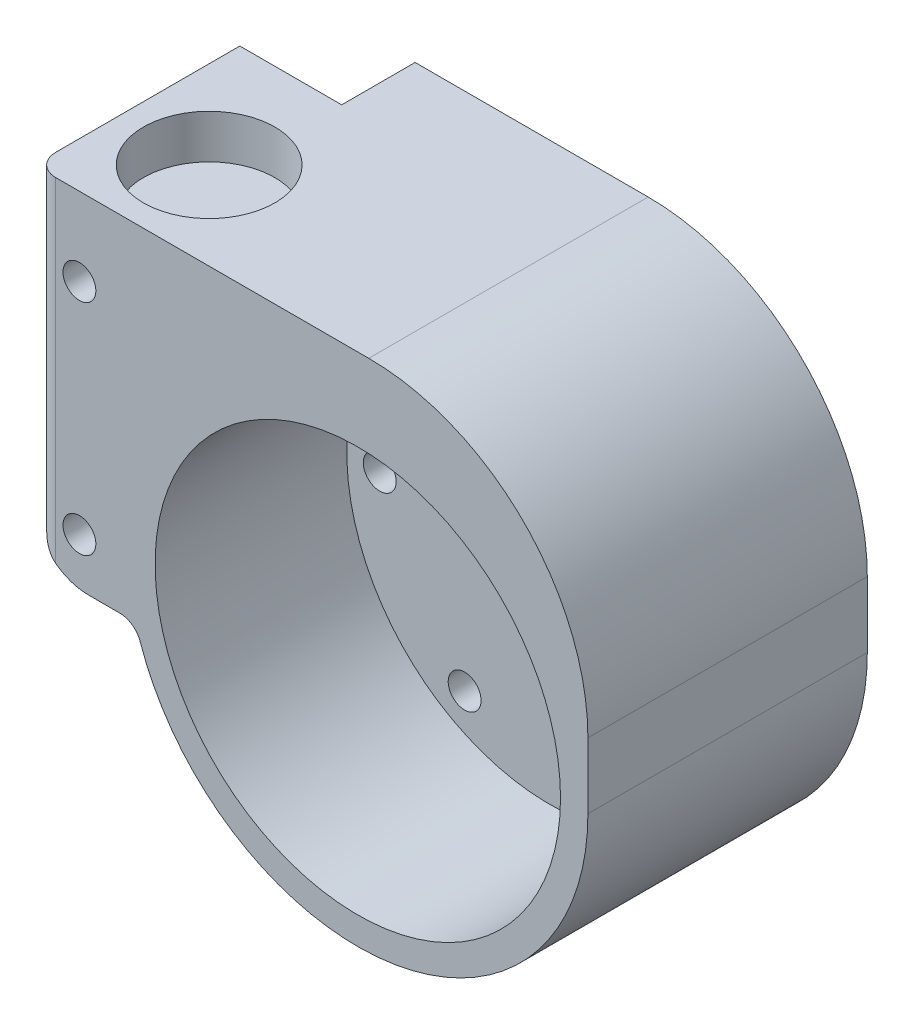
SolidWorks part; units mm, degrees
ref_plane "前视基准面" through (0, 0, 0) normal (0, 0, 1) x (1, 0, 0)
ref_plane "上视基准面" through (0, 0, 0) normal (0, 1, 0) x (1, 0, 0)
ref_plane "右视基准面" through (0, 0, 0) normal (1, 0, 0) x (0, 0, -1)
sketch "草图1" plane through (0, 0, 0) normal (0, 0, 1) x (1, 0, 0)
  line L0 (0, 0) -> (11.7722, 20.39) construction
  line L1 (-21, 0) -> (21, 0)
  line L2 (-21, 0) -> (-21, 26)
  line L3 (-21, 26) -> (21, 26)
  line L4 (21, 0) -> (21, 26)
  line L14 (-29.567, 26) -> (-20.267, 26)
  line L15 (-29.567, 26) -> (-29.567, -5.5)
  line L16 (-29.567, -5.5) -> (-20.267, -5.5)
  line L17 (-20.267, 26) -> (-20.267, -5.5)
  circle A0 centre (0, 0) radius 18.5 construction
  circle A1 centre (0, 0) radius 21
  circle A2 centre (0, 7) radius 6.25
  circle A3 centre (0, 0) radius 15.5
  circle A4 centre (7.75, 13.4234) radius 1.5
  circle A5 centre (15.5, 0) radius 1.5
  circle A6 centre (7.75, -13.4234) radius 1.5
  circle A7 centre (-7.75, -13.4234) radius 1.5
  circle A8 centre (-15.5, 0) radius 1.5
  circle A9 centre (-7.75, 13.4234) radius 1.5
  point P27 (0, 0)
  dimension "D1" = 37
  dimension "D2" = 42
  dimension "D3" = 12.5
  dimension "D5" = 31
  dimension "D6" = 3
  dimension "D4" = 7
  dimension "D7" = 60
  dimension "D9" = 26
  dimension "D10" = 9.3
  dimension "D11" = 31.5
  dimension "D8" = 6
extrude "凸台-拉伸1" add sketch "草图1" along normal blind 25.5 contours A9 A3 A8 L1 A5 A4 | A8 A3 A7 A6 A5 L1 A2 | A8 L17 A1 L1 A5 A3 A6 A7 | A9 A3 A4 A5 L1 A1 L17 A8 | A1 L4 L3 L17 | A8 L1 A1 L17 | A8 L17 A1 L1 | A1 L17 L3 L2 | A1 L2 L14 L15 L16 region at (16.8541, 1.4213, 0) region at (19, -0.463, 0) region at (0, -6.516, 0) region at (0, 0.3453, 0) region at (2.8388, 21.2994, 0) region at (-20.5606, -2.0674, 0) region at (-25.2613, 10.1792, 0) region at (-20.6455, 14.8023, 0) region at (-20.5606, 2.0674, 0)
sketch "草图2" plane through (0, 0, 25.5) normal (0, 0, 1) x (1, 0, 0)
  circle A0 centre (0, 0) radius 18.5
  dimension "D1" = 37
extrude "切除-拉伸1" cut sketch "草图2" against normal blind 17.5
sketch "草图3" plane through (0, 0, 0) normal (0, 0, -1) x (-1, 0, 0)
  line L0 (29.567, 26) -> (-21, 26) construction
  line L1 (20.27, 26) -> (29.57, 26)
  line L2 (20.27, 26) -> (20.27, -5.5)
  line L3 (20.27, -5.5) -> (29.57, -5.5)
  line L4 (29.57, 26) -> (29.57, -5.5)
  line L5 (29.567, -5.5) -> (20.267, -5.5) construction
  line L6 (29.567, -5.5) -> (20.267, -5.5) construction
  dimension "D1" = 9.3
  dimension "D2" = 31.5
  dimension "D3" = 20.27
extrude "切除-拉伸2" cut sketch "草图3" against normal blind 6.7
fillet "圆角1" radius 20 1 edges at (21, 26, 12.75)
sketch "草图4" plane through (0, 0, 6.7) normal (0, 0, -1) x (-1, 0, 0)
  line L0 (25.4073, 23.6329) -> (25.4073, 16.3035) construction
  line L2 (29.567, 26) -> (20.27, 26) construction
  circle A0 centre (25.4073, 18.87) radius 1.5
  circle A1 centre (25.4073, -1.13) radius 1.5
  dimension "D3" = 3
  dimension "D4" = 3
  dimension "D1" = 7.13
  dimension "D2" = 20
extrude "切除-拉伸3" cut sketch "草图4" against normal through all
fillet "圆角3" radius 2 1 edges at (-29.567, 10.25, 25.5)
fillet "圆角4" radius 2 1 edges at (-20.267, -5.5, 12.75)
fillet "圆角5" radius 5 1 edges at (-29.567, -5.5, 15.1) tangent propagation no
sketch "草图5" plane through (0, 26, 0) normal (0, 1, 0) x (1, 0, 0)
  line L0 (-27.567, -25.5) -> (1, -25.5) construction
  line L1 (-29.567, -23.5) -> (-29.567, -6.7) construction
  circle A0 centre (-21.567, -17.5) radius 6
  point P2 (-19.6119, -15.0363)
  point P7 (-28.8202, -14.0893)
  point P8 (0, 0)
  dimension "D1" = 12
  dimension "D2" = 8
  dimension "D3" = 8
extrude "切除-拉伸4" cut sketch "草图5" against normal blind 4
sketch "草图6" plane through (-29.567, 0, 0) normal (-1, 0, 0) x (0, 0, 1)
  line L0 (23.5, 26) -> (6.7, 26) construction
  line L1 (10.1, 13.87) -> (20.1, 13.87) construction
  line L2 (10.1, 13.87) -> (10.1, 3.87) construction
  line L3 (10.1, 3.87) -> (20.1, 3.87) construction
  line L4 (20.1, 13.87) -> (20.1, 3.87) construction
  circle A0 centre (20.1, 13.87) radius 1.3
  circle A1 centre (20.1, 3.87) radius 1.3
  circle A2 centre (10.1, 3.87) radius 1.3
  circle A3 centre (10.1, 13.87) radius 1.3
  point P8 (10.1, 8.87)
  point P12 (15.1, 26)
  point P13 (15.1, 13.87)
  dimension "D3" = 2.6
  dimension "D4" = 2.6
  dimension "D5" = 2.6
  dimension "D6" = 2.6
  dimension "D1" = 10
  dimension "D2" = 10
  dimension "D7" = 17.13
extrude "切除-拉伸5" cut sketch "草图6" against normal blind 3
